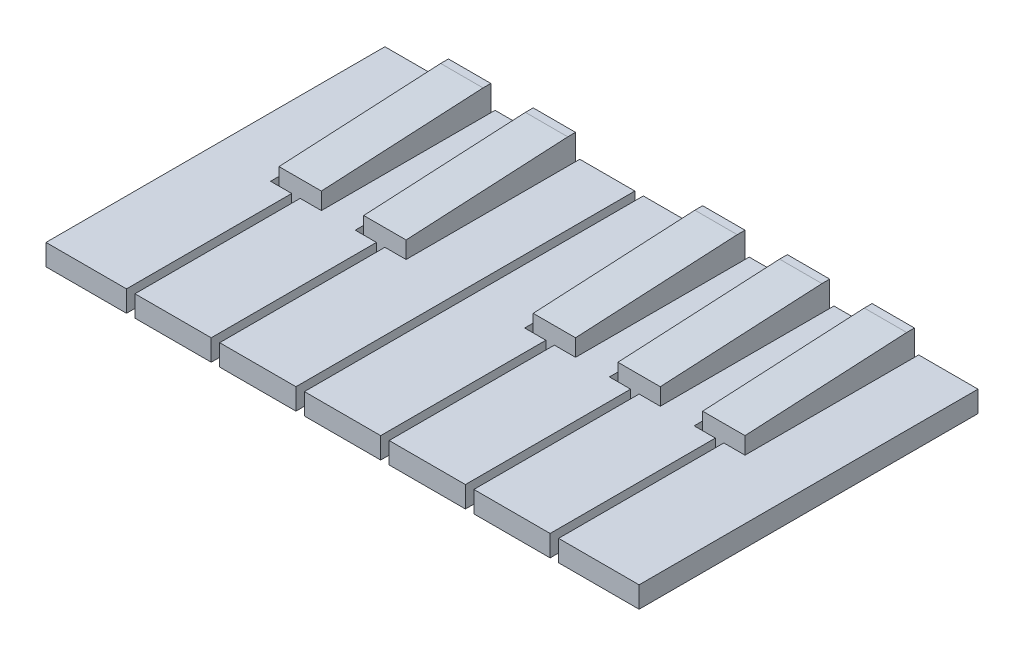
SolidWorks part; units mm, degrees
ref_plane "Front Plane" through (0, 0, 0) normal (0, 0, 1) x (1, 0, 0)
ref_plane "Top Plane" through (0, 0, 0) normal (0, 1, 0) x (1, 0, 0)
ref_plane "Right Plane" through (0, 0, 0) normal (1, 0, 0) x (0, 0, -1)
sketch "Sketch1" plane through (0, 0, 0) normal (0, 1, 0) x (1, 0, 0)
  line L0 (0, 0) -> (0, 80)
  line L1 (0, 80) -> (15, 80)
  line L2 (15, 80) -> (15, 40)
  line L3 (15, 40) -> (25, 40)
  line L4 (25, 40) -> (25, 80)
  line L5 (25, 80) -> (35, 80)
  line L6 (35, 80) -> (35, 40)
  line L7 (35, 40) -> (45, 40)
  line L8 (45, 40) -> (45, 80)
  line L9 (45, 80) -> (60, 80)
  line L10 (60, 80) -> (75, 80)
  line L11 (75, 80) -> (75, 40)
  line L12 (75, 40) -> (85, 40)
  line L13 (85, 40) -> (85, 80)
  line L14 (85, 80) -> (95, 80)
  line L15 (95, 80) -> (95, 40)
  line L16 (95, 40) -> (105, 40)
  line L17 (105, 40) -> (105, 80)
  line L18 (105, 80) -> (115, 80)
  line L19 (115, 80) -> (115, 40)
  line L20 (115, 40) -> (125, 40)
  line L21 (125, 40) -> (125, 80)
  line L22 (125, 80) -> (140, 80)
  line L23 (140, 80) -> (140, 0)
  line L24 (140, 0) -> (0, 0)
  line L25 (60, 80) -> (60, 0)
  line L26 (40, 40) -> (40, 0)
  line L27 (20, 40) -> (20, 0)
  line L28 (80, 40) -> (80, 0)
  line L29 (100, 40) -> (100, 0)
  line L30 (120, 40) -> (120, 0)
  line L31 (15, 80) -> (25, 80)
  line L32 (35, 80) -> (45, 80)
  line L33 (75, 80) -> (85, 80)
  line L34 (95, 80) -> (105, 80)
  line L35 (115, 80) -> (125, 80)
  line L36 (19, 39) -> (14, 39)
  line L37 (21, 0) -> (19, 0)
  line L38 (21, 0) -> (21, 40)
  line L39 (21, 40) -> (19, 40)
  line L40 (19, 0) -> (19, 40)
  line L41 (21, 0) -> (19, 40) construction
  line L42 (21, 40) -> (19, 0) construction
  line L43 (41, 0) -> (39, 0)
  line L44 (41, 0) -> (41, 40)
  line L45 (41, 40) -> (39, 40)
  line L46 (39, 0) -> (39, 40)
  line L47 (41, 0) -> (39, 40) construction
  line L48 (41, 40) -> (39, 0) construction
  line L49 (61, 0) -> (59, 0)
  line L50 (61, 0) -> (61, 80)
  line L51 (61, 80) -> (59, 80)
  line L52 (59, 0) -> (59, 80)
  line L53 (61, 0) -> (59, 80) construction
  line L54 (61, 80) -> (59, 0) construction
  line L55 (81, 0) -> (79, 0)
  line L56 (81, 0) -> (81, 40)
  line L57 (81, 40) -> (79, 40)
  line L58 (79, 0) -> (79, 40)
  line L59 (81, 0) -> (79, 40) construction
  line L60 (81, 40) -> (79, 0) construction
  line L61 (101, 0) -> (99, 0)
  line L62 (101, 0) -> (101, 40)
  line L63 (101, 40) -> (99, 40)
  line L64 (99, 0) -> (99, 40)
  line L65 (101, 0) -> (99, 40) construction
  line L66 (101, 40) -> (99, 0) construction
  line L67 (121, 0) -> (119, 0)
  line L68 (121, 0) -> (121, 40)
  line L69 (121, 40) -> (119, 40)
  line L70 (119, 0) -> (119, 40)
  line L71 (121, 0) -> (119, 40) construction
  line L72 (121, 40) -> (119, 0) construction
  line L73 (14, 39) -> (14, 80)
  line L74 (21, 39) -> (26, 39)
  line L75 (26, 39) -> (26, 80)
  line L76 (39, 39) -> (34, 39)
  line L77 (34, 39) -> (34, 80)
  line L78 (41, 39) -> (46, 39)
  line L79 (46, 39) -> (46, 80)
  line L80 (79, 39) -> (74, 39)
  line L81 (74, 39) -> (74, 80)
  line L82 (81, 39) -> (86, 39)
  line L83 (86, 39) -> (86, 80)
  line L84 (94, 80) -> (94, 39)
  line L85 (94, 39) -> (99, 39)
  line L86 (101, 39) -> (106, 39)
  line L87 (106, 39) -> (106, 80)
  line L88 (114, 80) -> (114, 39)
  line L89 (114, 39) -> (119, 39)
  line L90 (121, 39) -> (126, 39)
  line L91 (126, 39) -> (126, 80)
  point P37 (20, 20)
  point P42 (40, 20)
  point P47 (60, 40)
  point P52 (80, 20)
  point P57 (100, 20)
  point P62 (120, 20)
  dimension "D1" = 10
  dimension "D2" = 10
  dimension "D3" = 10
  dimension "D4" = 10
  dimension "D5" = 10
  dimension "D6" = 15
  dimension "D7" = 10
  dimension "D8" = 30
  dimension "D9" = 10
  dimension "D10" = 10
  dimension "D11" = 15
  dimension "D12" = 40
  dimension "D13" = 80
  dimension "D14" = 40
  dimension "D15" = 40
  dimension "D16" = 40
  dimension "D17" = 40
  dimension "D18" = 40
  dimension "D19" = 40
  dimension "D20" = 40
  dimension "D21" = 40
  dimension "D22" = 40
  dimension "D23" = 15
  dimension "D24" = 1
  dimension "D25" = 1
  dimension "D26" = 1
  dimension "D27" = 1
  dimension "D28" = 1
  dimension "D29" = 1
  dimension "D30" = 1
  dimension "D31" = 1
  dimension "D32" = 1
  dimension "D33" = 1
  dimension "D34" = 1
  dimension "D35" = 1
  dimension "D36" = 1
  dimension "D37" = 1
  dimension "D38" = 1
  dimension "D39" = 1
  dimension "D40" = 1
  dimension "D41" = 1
  dimension "D42" = 1
extrude "Boss-Extrude1" add sketch "Sketch1" along normal blind 10 contours L31 L2 L3 L4 | L32 L6 L7 L8 | L33 L11 L12 L13 | L34 L15 L16 L17 | L35 L19 L20 L21 region at (20, 0, -60) region at (40, 0, -60) region at (80, 0, -60) region at (100, 0, -60) region at (120, 0, -60)
extrude "Boss-Extrude2" add sketch "Sketch1<3>" along normal blind 5 contours L36 L73 L1 L0 L24 L40 | L76 L77 L5 L75 L74 L38 L24 L46 | L79 L78 L44 L24 L52 L9 | L80 L81 L10 L50 L24 L58 | L85 L84 L14 L83 L82 L56 L24 L64 | L89 L88 L18 L87 L86 L62 L24 L70 | L91 L90 L68 L24 L23 L22 region at (8.4087, 0, -36.9601) region at (30, 0, -32.2379) region at (51.0789, 0, -36.7632) region at (68.9211, 0, -36.7632) region at (90, 0, -32.2379) region at (110, 0, -32.2379) region at (131.5913, 0, -36.9601)
sketch "Sketch1<3>" plane through (0, 0, 0) normal (0, 1, 0) x (1, 0, 0) same geometry as "Sketch1"
chamfer "Chamfer1" distance 2 angle 87 1 edges at (20, 10, -40) first distance on face at (20, 5, -40)
chamfer "Chamfer2" distance 2 angle 87 1 edges at (40, 10, -40) first distance on face at (40, 5, -40)
chamfer "Chamfer3" distance 2 angle 87 1 edges at (80, 10, -40) first distance on face at (80, 5, -40)
chamfer "Chamfer4" distance 2 angle 87 1 edges at (100, 10, -40) first distance on face at (100, 5, -40)
chamfer "Chamfer5" distance 2 angle 87 1 edges at (120, 10, -40) first distance on face at (120, 5, -40)
